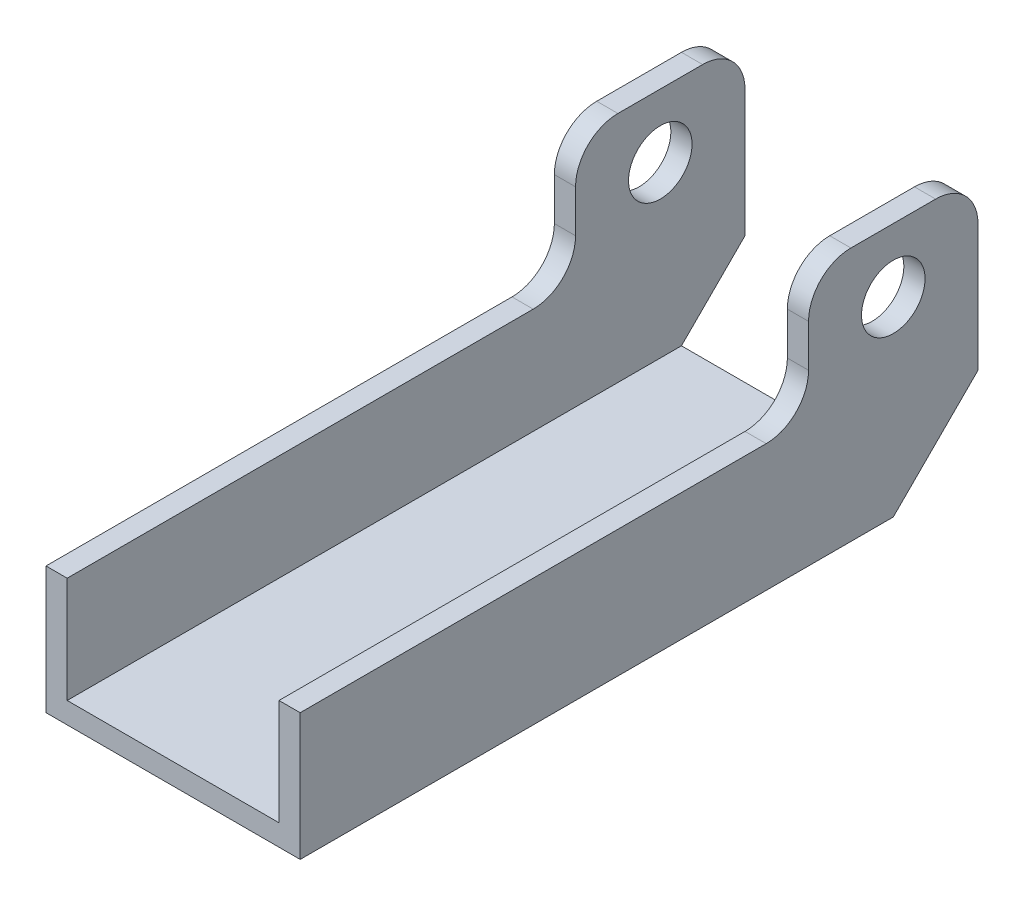
SolidWorks part; units mm, degrees
material "1060 Alloy"
ref_plane "Front" through (0, 0, 0) normal (0, 0, 1) x (1, 0, 0)
ref_plane "Top" through (0, 0, 0) normal (0, 1, 0) x (1, 0, 0)
ref_plane "Right" through (0, 0, 0) normal (1, 0, 0) x (0, 0, -1)
sketch "Sketch1" plane through (0, 0, 0) normal (0, 0, 1) x (1, 0, 0)
  line L0 (17.4625, 9.525) -> (17.4625, 1.5875)
  line L1 (0, 0) -> (19.05, 0)
  line L2 (0, 0) -> (0, 9.525)
  line L7 (0, 9.525) -> (1.5875, 9.525)
  line L9 (17.4625, 9.525) -> (19.05, 9.525)
  line L12 (19.05, 9.525) -> (19.05, 0)
  line L13 (17.4625, 1.5875) -> (1.5875, 1.5875)
  line L14 (1.5875, 1.5875) -> (1.5875, 9.525)
  dimension "D1" = 1.5875
  dimension "D2" = 1.5875
  dimension "D3" = 9.525
  dimension "D4" = 19.05
extrude "Boss-Extrude1" add sketch "Sketch1" along normal blind 50.8
sketch "Sketch4" plane through (0, 9.525, 0) normal (0, 1, 0) x (1, 0, 0)
  line L0 (1.5875, -50.8) -> (1.5875, 0) construction
  line L1 (0, 0) -> (1.5875, 0)
  line L2 (0, 0) -> (0, -12.7)
  line L3 (0, -12.7) -> (1.5875, -12.7)
  line L4 (1.5875, 0) -> (1.5875, -12.7)
  line L5 (19.05, -50.8) -> (19.05, 0) construction
  line L6 (17.4625, 0) -> (19.05, 0)
  line L7 (17.4625, 0) -> (17.4625, -12.7)
  line L8 (17.4625, -12.7) -> (19.05, -12.7)
  line L9 (19.05, 0) -> (19.05, -12.7)
  dimension "D1" = 12.7
extrude "Boss-Extrude2" add sketch "Sketch4" along normal blind 9.525
fillet "Fillet2" radius 3.175 6 edges at (18.2563, 9.525, 12.7) (0.7937, 9.525, 12.7) (0.7938, 19.05, 12.7) (18.2563, 19.05, 12.7) (18.2563, 19.05, 0) (0.7937, 19.05, 0)
hole_wizard "3/16 (0.1875) Diameter Hole1" positions "Sketch2" profile "Sketch3" hole size "3/16" standard "ANSI Inch" end condition through all
sketch "Sketch2" plane through (19.05, 0, 0) normal (1, 0, 0) x (0, 0, -1)
  line L0 (0, 0) -> (0, 15.875) construction
  line L2 (-9.525, 19.05) -> (-3.175, 19.05) construction
  point P0 (-6.35, 14.2875)
  point P10 (4.1158, 15.875)
  dimension "D1" = 6.35
  dimension "D2" = 4.7625
sketch "Sketch3" plane through (19.05, 14.2875, 6.35) normal (0, 1, 0) x (0, 0, -1)
  line L0 (0, 0) -> (0, 19.05)
  line L1 (0, 19.05) -> (2.3812, 19.05)
  line L2 (2.3812, 19.05) -> (2.3812, 0)
  line L5 (2.3812, 0) -> (0, 0)
  line L11 (0, -6.35) -> (0, 107.95) construction
  dimension "Thru Hole Dia." = 4.7625
  dimension "Thru Hole Depth" = 19.05
chamfer "Chamfer1" distance 6.35 angle 45 1 edges at (9.525, 0, 0)
